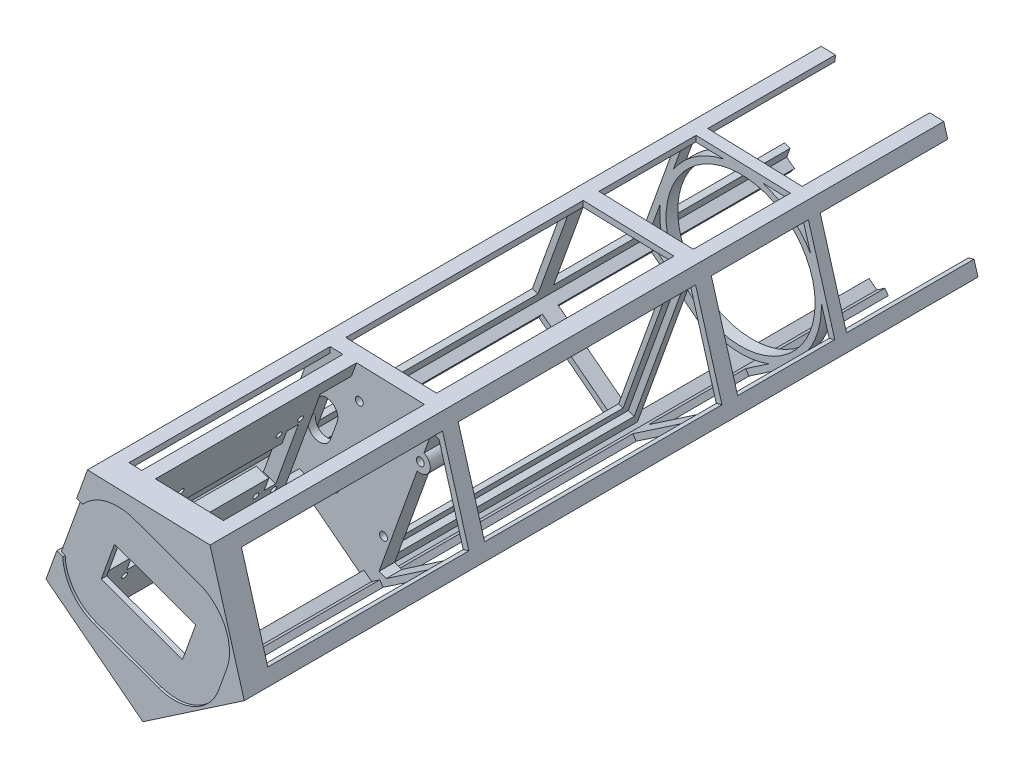
SolidWorks part; units mm, degrees
ref_plane "Front Plane" through (0, 0, 0) normal (0, 0, 1) x (1, 0, 0)
ref_plane "Top Plane" through (0, 0, 0) normal (0, 1, 0) x (1, 0, 0)
ref_plane "Right Plane" through (0, 0, 0) normal (1, 0, 0) x (0, 0, -1)
sketch "Sketch3" plane through (0, 0, 0) normal (0, 0, 1) x (1, 0, 0)
  line L0 (0, 0) -> (16.2851, 21.0012) construction
  line L1 (15.1489, 19.536) -> (-13.8986, 20.4445)
  line L2 (-13.8986, 20.4445) -> (-23.7387, -6.9006)
  line L3 (-23.7387, -6.9006) -> (-0.7728, -24.7093)
  line L4 (-0.7728, -24.7093) -> (23.2611, -8.3705)
  line L5 (0, 0) -> (29.9163, 0) construction
  line L6 (0, 0) -> (25.0057, -8.9983) construction
  line L10 (-0.8307, -26.5625) -> (25.0057, -8.9983)
  line L11 (25.0057, -8.9983) -> (16.2851, 21.0012)
  line L12 (16.2851, 21.0012) -> (-14.941, 21.9778)
  line L13 (-14.941, 21.9778) -> (-25.5191, -7.4182)
  line L14 (-25.5191, -7.4182) -> (-0.8307, -26.5625)
  line L15 (23.2611, -8.3705) -> (15.1489, 19.536)
  circle A0 centre (0, 0) radius 20 construction
  dimension "D2" = 40
extrude "Boss-Extrude2" add sketch "Sketch3" along normal blind 185
ref_plane "Plane1" through (0, 0, 92.5) normal (0, 0, 1) x (1, 0, 0)
sketch "Sketch4" plane through (0, 0, 0) normal (0, 0, -1) x (-1, 0, 0)
  line L0 (14.745, 18.0921) -> (16.1564, 18.6)
  line L1 (13.8986, 20.4445) -> (23.7387, -6.9006) construction
  line L2 (14.941, 21.9778) -> (25.5191, -7.4182) construction
  line L3 (24.3036, -4.0404) -> (22.8922, -4.5483)
  line L4 (22.8922, -4.5483) -> (14.745, 18.0921)
  line L5 (24.3036, -4.0404) -> (16.1564, 18.6)
  dimension "D1" = 2.5
  dimension "D2" = 2.5
extrude "Cut-Extrude1" cut sketch "Sketch4" against normal offset from surface (180 mm away) 5 up to face at (0, 0, 185)
ref_point "Point1"
ref_axis "Axis1" through (0, 0, 185) along (0, 0, 1)
pattern_circular "CirPattern1" count 5 over 360 about axis through (0, 0, 185) along (0, 0, 1) of "Cut-Extrude1"
ref_plane "Plane2" through (0, 0, 92.5) normal (0, 0, 1) x (1, 0, 0)
sketch "Sketch5" plane through (0, 0, 92.5) normal (0, 0, 1) x (1, 0, 0)
  line L0 (-2.0696, -25.6018) -> (14.7182, 21.0502) construction
  line L2 (-24.1133, -8.5083) -> (-1.8275, -25.7895) construction
  line L3 (23.2611, -8.3705) -> (0, 0) construction
  line L4 (-4.3961, -23.7977) -> (11.7756, 21.1422)
  line L8 (-2.0696, -25.6018) -> (-4.3961, -23.7977)
  line L10 (14.7182, 21.0502) -> (11.7756, 21.1422)
  line L11 (-2.0696, -25.6018) -> (14.7182, 21.0502)
  line L12 (-22.8004, 22.2236) -> (6.2471, 21.3151) construction
  dimension "D1" = 18
  dimension "D2" = 2.8
extrude "Boss-Extrude3" add sketch "Sketch5" along normal mid plane 64.5
sketch "Sketch6" plane through (0, 0, 124.75) normal (0, 0, 1) x (1, 0, 0)
  line L5 (-25.5191, -7.4182) -> (-0.8307, -26.5625)
  line L6 (-0.8307, -26.5625) -> (25.0057, -8.9983)
  line L7 (25.0057, -8.9983) -> (16.2851, 21.0012)
  line L8 (16.2851, 21.0012) -> (-14.941, 21.9778)
  line L9 (-14.941, 21.9778) -> (-25.5191, -7.4182)
  line L10 (-25.5191, -7.4182) -> (-0.8307, -26.5625)
  line L11 (-0.8307, -26.5625) -> (25.0057, -8.9983)
  line L12 (25.0057, -8.9983) -> (16.2851, 21.0012)
  line L13 (16.2851, 21.0012) -> (-14.941, 21.9778)
  line L14 (-14.941, 21.9778) -> (-25.5191, -7.4182)
  dimension "D1" = 0
extrude "Boss-Extrude4" add sketch "Sketch6" along normal blind 4
sketch "Sketch7" plane through (0, 0, 124.75) normal (0, 0, -1) x (-1, 0, 0)
  line L0 (-3.6897, -1.3278) -> (20.23, 7.2798) construction
  line L1 (-11.7756, 21.1422) -> (4.3961, -23.7977) construction
  line L2 (16.1564, 18.6) -> (24.3036, -4.0404) construction
  line L4 (19.0326, -2.4504) -> (13.1071, 14.0159)
  line L5 (0.2139, -9.2223) -> (-5.7115, 7.244)
  line L7 (19.0326, -2.4504) -> (-5.7115, 7.244) construction
  line L8 (0.2139, -9.2223) -> (13.1071, 14.0159) construction
  line L9 (9.6232, -5.8364) -> (3.6978, 10.63) construction
  line L11 (-11.7756, 21.1422) -> (4.3961, -23.7977) construction
  arc A0 (-5.7115, 7.244) -> (13.1071, 14.0159) centre (3.6978, 10.63) cw
  arc A1 (0.2139, -9.2223) -> (19.0326, -2.4504) centre (9.6232, -5.8364) ccw
  point P7 (6.6605, 2.3968)
  point P9 (13.0092, -15.2457)
  point P14 (0.3119, 20.0393)
  dimension "D1" = 37.5
  dimension "D2" = 20
  dimension "D3" = 1
extrude "Cut-Extrude2" cut sketch "Sketch7" against normal blind 2
sketch "Sketch8" plane through (6.3243, -2.2758, 0) normal (0.9409, -0.3386, 0) x (0, 0, -1)
  line L0 (-60.25, 0) -> (-124.75, 0) construction
  line L1 (-124.75, -23.2131) -> (-124.75, 23.2131) construction
  line L3 (-60.25, -23.2131) -> (-60.25, 23.2131) construction
  line L5 (-123, -20.5) -> (-123, 20.5)
  line L6 (-123, -20.5) -> (-62, -20.5)
  line L7 (-123, 20.5) -> (-62, 20.5)
  line L8 (-62, -20.5) -> (-62, 20.5)
  line L14 (-62, 20.5) -> (-123, -20.5) construction
  line L15 (-62, -20.5) -> (-123, 20.5) construction
  point P11 (-92.5, 0)
  point P14 (-92.5, 0)
  dimension "D1" = 61
  dimension "D2" = 41
extrude "Cut-Extrude3" cut sketch "Sketch8" against normal blind 1.6
sketch "Sketch9" plane through (4.8189, -1.7341, 0) normal (0.9409, -0.3386, 0) x (0, 0, -1)
  line L8 (-121, -18.5) -> (-64, -18.5)
  line L9 (-64, -18.5) -> (-64, 18.5)
  line L10 (-64, 18.5) -> (-121, 18.5)
  line L11 (-121, 18.5) -> (-121, -18.5)
  line L12 (-121, -18.5) -> (-64, -18.5)
  line L13 (-64, -18.5) -> (-64, 18.5)
  line L14 (-64, 18.5) -> (-121, 18.5)
  line L15 (-121, 18.5) -> (-121, -18.5)
  dimension "D1" = 2
extrude "Cut-Extrude4" cut sketch "Sketch9" against normal up to surface (1.2 mm away) up to face at (3.6897, -1.3278, 92.5)
sketch "Sketch10" plane through (0, 0, 60.25) normal (0, 0, -1) x (-1, 0, 0)
  line L25 (-23.2611, -8.3705) -> (0.7728, -24.7093)
  line L26 (0.7728, -24.7093) -> (23.7387, -6.9006)
  line L27 (23.7387, -6.9006) -> (13.8986, 20.4445)
  line L28 (13.8986, 20.4445) -> (-15.1489, 19.536)
  line L29 (-15.1489, 19.536) -> (-23.2611, -8.3705)
  line L30 (0.8307, -26.5625) -> (25.5191, -7.4182)
  line L31 (-25.0057, -8.9983) -> (0.8307, -26.5625)
  line L32 (-16.2851, 21.0012) -> (-25.0057, -8.9983)
  line L33 (14.941, 21.9778) -> (-16.2851, 21.0012)
  line L34 (25.5191, -7.4182) -> (14.941, 21.9778)
  line L40 (0.8307, -26.5625) -> (25.5191, -7.4182)
  line L41 (-25.0057, -8.9983) -> (0.8307, -26.5625)
  line L42 (-16.2851, 21.0012) -> (-25.0057, -8.9983)
  line L43 (14.941, 21.9778) -> (-16.2851, 21.0012)
  line L44 (25.5191, -7.4182) -> (14.941, 21.9778)
  dimension "D1" = 0
extrude "Boss-Extrude5" add sketch "Sketch10" against normal blind 4
sketch "Sketch11" plane through (0, 0, 60.25) normal (0, 0, -1) x (-1, 0, 0)
  line L0 (3.8621, -22.3137) -> (4.3961, -23.7977)
  line L1 (4.3961, -23.7977) -> (3.6676, -24.3627)
  line L2 (-11.2416, 19.6582) -> (-11.7756, 21.1422)
  line L3 (-11.7756, 21.1422) -> (-12.697, 21.1134)
  line L4 (21.7631, -8.4326) -> (3.8621, -22.3137)
  line L7 (3.8621, -22.3137) -> (-11.2416, 19.6582)
  line L9 (-14.1842, 19.5662) -> (1.5355, -24.1178)
  line L10 (-14.1842, 19.5662) -> (1.5355, -24.1178)
  line L11 (-12.697, 21.1134) -> (11.3529, 21.8656) construction
  line L13 (3.8621, -22.3137) -> (-11.2416, 19.6582) construction
  line L18 (22.6823, -9.618) -> (3.6676, -24.3627) construction
  line L19 (3.8621, -22.3137) -> (-11.2416, 19.6582)
  line L27 (-11.2416, 19.6582) -> (11.3998, 20.3663)
  line L31 (1.5355, -24.1178) -> (2.7484, -23.1773)
  line L33 (1.5355, -24.1178) -> (2.7484, -23.1773)
  line L35 (2.7484, -23.1773) -> (3.6676, -24.3627)
  line L37 (2.7484, -23.1773) -> (3.6676, -24.3627)
  line L39 (3.6676, -24.3627) -> (22.6823, -9.618)
  line L41 (22.6823, -9.618) -> (21.7631, -8.4326)
  line L43 (11.3998, 20.3663) -> (11.3529, 21.8656)
  line L45 (11.3529, 21.8656) -> (-12.697, 21.1134)
  line L47 (-12.697, 21.1134) -> (-12.6502, 19.6141)
  line L48 (-12.697, 21.1134) -> (-12.6502, 19.6141)
  line L49 (-12.6502, 19.6141) -> (-14.1842, 19.5662)
  line L50 (-12.6502, 19.6141) -> (-14.1842, 19.5662)
  dimension "D1" = 0
ref_plane "Plane3" through (0, 0, 32.5) normal (0, 0, 1) x (1, 0, 0)
sketch "Sketch14" plane through (0, 0, 32.5) normal (0, 0, 1) x (1, 0, 0)
  line L5 (-25.5191, -7.4182) -> (-0.8307, -26.5625)
  line L6 (-0.8307, -26.5625) -> (25.0057, -8.9983)
  line L7 (25.0057, -8.9983) -> (16.2851, 21.0012)
  line L8 (16.2851, 21.0012) -> (-14.941, 21.9778)
  line L9 (-14.941, 21.9778) -> (-25.5191, -7.4182)
  line L11 (-0.8307, -26.5625) -> (25.0057, -8.9983)
  line L12 (25.0057, -8.9983) -> (16.2851, 21.0012)
  line L16 (23.2611, -8.3705) -> (15.3259, -13.7651)
  line L18 (-0.7728, -24.7093) -> (-8.3554, -18.8294)
  line L20 (-23.7387, -6.9006) -> (-20.4898, 2.1279)
  line L22 (-13.8986, 20.4445) -> (-4.308, 20.1445)
  line L24 (15.1489, 19.536) -> (17.8273, 10.3221)
  line L25 (7.1625, -19.3147) -> (-0.7728, -24.7093)
  line L26 (20.5827, 0.8433) -> (23.2611, -8.3705)
  line L27 (5.5584, 19.8359) -> (15.1489, 19.536)
  line L28 (-17.1475, 11.416) -> (-13.8986, 20.4445)
  line L29 (-16.1561, -12.7805) -> (-23.7387, -6.9006)
  line L30 (16.2851, 21.0012) -> (-14.941, 21.9778)
  line L31 (-14.941, 21.9778) -> (-25.5191, -7.4182)
  line L32 (-25.5191, -7.4182) -> (-0.8307, -26.5625)
  circle A3 centre (0, 0) radius 19
  arc A8 (15.3259, -13.7651) -> (20.5827, 0.8433) centre (0, 0) ccw
  circle A9 centre (0, 0) radius 20.6 construction
  arc A10 (17.8273, 10.3221) -> (5.5584, 19.8359) centre (0, 0) ccw
  arc A11 (-4.308, 20.1445) -> (-17.1475, 11.416) centre (0, 0) ccw
  arc A12 (-20.4898, 2.1279) -> (-16.1561, -12.7805) centre (0, 0) ccw
  arc A13 (-8.3554, -18.8294) -> (7.1625, -19.3147) centre (0, 0) ccw
  dimension "D2" = 38
  dimension "D1" = 0
  dimension "D3" = 1.6
extrude "Boss-Extrude8" add sketch "Sketch14" along normal blind 3
ref_plane "Plane4" through (0, 0, 29.5) normal (0, 0, -1) x (-1, 0, 0)
sketch "Sketch15" plane through (0, 0, 29.5) normal (0, 0, -1) x (-1, 0, 0)
  line L0 (-23.2611, -8.3705) -> (0.7728, -24.7093)
  line L1 (0.7728, -24.7093) -> (23.7387, -6.9006)
  line L2 (23.7387, -6.9006) -> (13.8986, 20.4445)
  line L3 (13.8986, 20.4445) -> (-15.1489, 19.536)
  line L4 (-15.1489, 19.536) -> (-23.2611, -8.3705)
  line L5 (0.8307, -26.5625) -> (25.5191, -7.4182)
  line L6 (-25.0057, -8.9983) -> (0.8307, -26.5625)
  line L7 (-16.2851, 21.0012) -> (-25.0057, -8.9983)
  line L8 (14.941, 21.9778) -> (-16.2851, 21.0012)
  line L9 (25.5191, -7.4182) -> (14.941, 21.9778)
  line L10 (0.8307, -26.5625) -> (25.5191, -7.4182)
  line L11 (-25.0057, -8.9983) -> (0.8307, -26.5625)
  line L12 (-16.2851, 21.0012) -> (-25.0057, -8.9983)
  line L13 (14.941, 21.9778) -> (-16.2851, 21.0012)
  line L14 (25.5191, -7.4182) -> (14.941, 21.9778)
  dimension "D1" = 0
sketch "Sketch29" plane through (0, 0, 185) normal (0, 0, 1) x (1, 0, 0)
  line L5 (-25.5191, -7.4182) -> (-0.8307, -26.5625)
  line L6 (-0.8307, -26.5625) -> (25.0057, -8.9983)
  line L7 (25.0057, -8.9983) -> (16.2851, 21.0012)
  line L8 (16.2851, 21.0012) -> (-14.941, 21.9778)
  line L9 (-14.941, 21.9778) -> (-25.5191, -7.4182)
  line L10 (-25.5191, -7.4182) -> (-0.8307, -26.5625)
  line L11 (-0.8307, -26.5625) -> (25.0057, -8.9983)
  line L12 (25.0057, -8.9983) -> (16.2851, 21.0012)
  line L13 (16.2851, 21.0012) -> (-14.941, 21.9778)
  line L14 (-14.941, 21.9778) -> (-25.5191, -7.4182)
  dimension "D1" = 0
extrude "Boss-Extrude13" add sketch "Sketch29" along normal blind 2
sketch "Sketch30" plane through (0, 0, 187) normal (0, 0, 1) x (1, 0, 0)
  line L0 (25.0057, -8.9983) -> (-20.23, 7.2798) construction
  line L1 (-14.941, 21.9778) -> (-25.5191, -7.4182) construction
  line L2 (3.1542, -17.0767) -> (-13.3121, -11.1513)
  line L3 (18.5086, -9.8487) -> (20.5401, -4.2031)
  line L4 (-20.5401, 4.2031) -> (-18.5086, 9.8487)
  line L5 (13.3121, 11.1513) -> (-3.1542, 17.0767)
  line L6 (14.4454, -21.1398) -> (-14.4454, 21.1398) construction
  line L7 (-24.6033, -7.0881) -> (24.6033, 7.0881) construction
  line L8 (19.5243, -7.0259) -> (-19.5243, 7.0259) construction
  arc A0 (18.5086, -9.8487) -> (3.1542, -17.0767) centre (7.2174, -5.7855) cw
  arc A1 (-18.5086, 9.8487) -> (-3.1542, 17.0767) centre (-7.2174, 5.7855) cw
  arc A2 (-13.3121, -11.1513) -> (-20.5401, 4.2031) centre (-9.2489, 0.1399) cw
  arc A3 (20.5401, -4.2031) -> (13.3121, 11.1513) centre (9.2489, -0.1399) ccw
  point P5 (0, 0)
  dimension "D3" = 12
  dimension "D1" = 30
  dimension "D2" = 41.5
extrude "Cut-Extrude8" cut sketch "Sketch30" against normal blind 0.6
sketch "Sketch31" plane through (0, 0, 186.4) normal (0, 0, 1) x (1, 0, 0)
  line L0 (25.0057, -8.9983) -> (0, 0) construction
  line L1 (12.0432, 0.9801) -> (8.6573, -8.4292)
  line L2 (12.0432, 0.9801) -> (-8.6573, 8.4292)
  line L3 (8.6573, -8.4292) -> (-12.0432, -0.9801)
  line L4 (-8.6573, 8.4292) -> (-12.0432, -0.9801)
  line L5 (12.0432, 0.9801) -> (-12.0432, -0.9801) construction
  line L6 (8.6573, -8.4292) -> (-8.6573, 8.4292) construction
  line L7 (-10.3503, 3.7246) -> (10.3503, -3.7246) construction
  dimension "D1" = 22
  dimension "D2" = 10
extrude "Cut-Extrude9" cut sketch "Sketch31" against normal up to surface (1.4 mm away) up to face at (0, 0, 185)
sketch "Sketch32" plane through (0, 0, 187) normal (0, 0, 1) x (1, 0, 0)
  line L0 (0, 0) -> (-36.3954, 13.0969) construction
  line L1 (-22.7695, 0.2228) -> (-21.2398, -0.3276)
  line L3 (-14.941, 21.9778) -> (-25.5191, -7.4182) construction
  line L4 (-17.6906, 14.3368) -> (-16.1609, 13.7863)
  line L5 (-18.5086, 9.8487) -> (-20.5401, 4.2031) construction
  line L6 (-18.5086, 9.8487) -> (-20.5401, 4.2031)
  line L7 (-17.6906, 14.3368) -> (-22.7695, 0.2228)
  arc A0 (-20.5401, 4.2031) -> (-13.3121, -11.1513) centre (-9.2489, 0.1399) ccw construction
  arc A1 (-20.5401, 4.2031) -> (-13.3121, -11.1513) centre (-9.2489, 0.1399) ccw construction
  arc A3 (-3.1542, 17.0767) -> (-18.5086, 9.8487) centre (-7.2174, 5.7855) ccw construction
  arc A4 (-16.1609, 13.7863) -> (-18.5086, 9.8487) centre (-7.2174, 5.7855) ccw
  arc A5 (-20.5401, 4.2031) -> (-21.2398, -0.3276) centre (-9.2489, 0.1399) ccw
  dimension "D1" = 7.5
extrude "Cut-Extrude11" cut sketch "Sketch32" against normal up to surface (0.6 mm away) up to face at (0, 0, 186.4)
sketch "Sketch34" plane through (0, 0, 186.4) normal (0, 0, 1) x (1, 0, 0)
  line L0 (-22.7695, 0.2228) -> (-17.6906, 14.3368)
  line L1 (-22.7695, 0.2228) -> (-22.0638, -0.0311)
  line L2 (-17.6906, 14.3368) -> (-16.9849, 14.0828)
  line L3 (-22.0638, -0.0311) -> (-16.9849, 14.0828)
  line L4 (-13.3121, -11.1513) -> (3.1542, -17.0767)
  line L5 (18.5086, -9.8487) -> (20.5401, -4.2031)
  line L6 (13.3121, 11.1513) -> (-3.1542, 17.0767)
  line L7 (-18.5086, 9.8487) -> (-20.5401, 4.2031)
  line L8 (-13.3121, -11.1513) -> (3.1542, -17.0767) construction
  line L9 (18.5086, -9.8487) -> (20.5401, -4.2031) construction
  line L10 (13.3121, 11.1513) -> (-3.1542, 17.0767) construction
  line L11 (-18.5086, 9.8487) -> (-20.5401, 4.2031) construction
  arc A4 (3.1542, -17.0767) -> (18.5086, -9.8487) centre (7.2174, -5.7855) ccw
  arc A5 (20.5401, -4.2031) -> (13.3121, 11.1513) centre (9.2489, -0.1399) ccw
  arc A6 (-3.1542, 17.0767) -> (-18.5086, 9.8487) centre (-7.2174, 5.7855) ccw
  arc A7 (-20.5401, 4.2031) -> (-13.3121, -11.1513) centre (-9.2489, 0.1399) ccw
  arc A8 (3.1542, -17.0767) -> (18.5086, -9.8487) centre (7.2174, -5.7855) ccw construction
  arc A9 (20.5401, -4.2031) -> (13.3121, 11.1513) centre (9.2489, -0.1399) ccw construction
  arc A10 (-3.1542, 17.0767) -> (-18.5086, 9.8487) centre (-7.2174, 5.7855) ccw construction
  arc A11 (-20.5401, 4.2031) -> (-13.3121, -11.1513) centre (-9.2489, 0.1399) ccw construction
  dimension "D1" = 0
sketch "Sketch38" plane through (0, 0, 124.75) normal (0, 0, -1) x (-1, 0, 0)
  line L5 (13.8986, 20.4445) -> (-15.1489, 19.536)
  line L6 (-15.1489, 19.536) -> (-23.2611, -8.3705)
  line L7 (-23.2611, -8.3705) -> (0.7728, -24.7093)
  line L8 (0.7728, -24.7093) -> (23.7387, -6.9006)
  line L9 (23.7387, -6.9006) -> (13.8986, 20.4445)
  line L11 (-16.3988, 15.2363) -> (-23.2611, -8.3705)
  line L12 (-23.2611, -8.3705) -> (-2.9303, -22.1919)
  line L16 (-1.0956, -21.5316) -> (-2.9303, -22.1919)
  line L17 (0.03, -24.6596) -> (-15.6897, 19.0244)
  line L18 (-1.0956, -21.5316) -> (-14.5641, 15.8965)
  line L19 (-14.5641, 15.8965) -> (-16.3988, 15.2363)
  dimension "D3" = 1.6
  dimension "D4" = 1.6
  dimension "D1" = 0
  dimension "D2" = 1.6
extrude "Cut-Extrude14" cut sketch "Sketch38" against normal up to surface (4 mm away) up to face at (0, 0, 128.75)
sketch "Sketch40" plane through (-18.8186, 6.7719, 0) normal (0.9409, -0.3386, 0) x (0, 0, -1)
  line L0 (-185, 14.5309) -> (-185, -14.5309) construction
  line L1 (-185, 7.5) -> (-183.5, 7.5)
  line L2 (-185, 7.5) -> (-185, -7.5)
  line L3 (-185, -7.5) -> (-183.5, -7.5)
  line L4 (-183.5, 7.5) -> (-183.5, -7.5)
  line L5 (-183.5, 0) -> (-185, 0) construction
  point P9 (-185, 0)
  dimension "D1" = 15
  dimension "D2" = 1.5
extrude "Cut-Extrude15" cut sketch "Sketch40" against normal up to surface (1.5 mm away) up to face at (-20.23, 7.2798, 98.8167)
sketch "Sketch41" plane through (-20.23, 7.2798, 0) normal (-0.9409, 0.3386, 0) x (0, 0, 1)
  line L0 (185, -7.5) -> (186.4, -7.5)
  line L1 (185, 7.5) -> (186.4, 7.5)
  line L2 (185, -7.5) -> (185, 7.5)
  line L3 (186.4, 7.5) -> (186.4, -7.5)
extrude "Cut-Extrude16" cut sketch "Sketch41" against normal blind 0.6
ref_plane "Plane5" through (14.5641, 15.8965, 124.75) normal (0.3386, 0.9409, 0) x (0.9409, -0.3386, 0)
sketch "Sketch42" plane through (0, 0, 128.75) normal (0, 0, 1) x (1, 0, 0)
  line L0 (-20.23, 7.2798) -> (0, 0) construction
  line L1 (-16.1564, 18.6) -> (-24.3036, -4.0404) construction
  line L2 (5.4365, -16.774) -> (-14.8782, -9.4637) construction
  line L3 (5.4365, -16.774) -> (14.8782, 9.4637) construction
  line L4 (-14.8782, -9.4637) -> (-5.4365, 16.774) construction
  line L5 (14.8782, 9.4637) -> (-5.4365, 16.774) construction
  line L6 (5.4365, -16.774) -> (-5.4365, 16.774) construction
  line L7 (-14.8782, -9.4637) -> (14.8782, 9.4637) construction
  line L8 (-3.9066, 13.524) -> (11.6282, 7.9338) construction
  line L9 (4.7208, 13.1189) -> (-4.7208, -13.1189) construction
  line L10 (2.2472, -13.2032) -> (-10.1449, -8.7439) construction
  line L11 (-1.5355, -24.1178) -> (14.1842, 19.5662) construction
  line L12 (-1.5355, -24.1178) -> (14.1842, 19.5662)
  line L13 (12.891, 3.9416) -> (6.1392, -14.8212) construction
  line L14 (12.891, 3.9416) -> (10.6328, 4.7542) construction
  line L15 (6.1392, -14.8212) -> (3.881, -14.0086) construction
  line L16 (10.6328, 4.7542) -> (3.881, -14.0086) construction
  circle A0 centre (11.6282, 7.9338) radius 1
  circle A1 centre (-3.9066, 13.524) radius 1
  circle A2 centre (2.2472, -13.2032) radius 1
  circle A3 centre (-10.1449, -8.7439) radius 1
  point P1 (3.8608, 10.7289)
  point P2 (0, 0)
  point P19 (-3.9488, -10.9735)
  dimension "D4" = 2
  dimension "D7" = 2
  dimension "D1" = 21.59
  dimension "D2" = 27.8848
  dimension "D3" = 16.51
  dimension "D5" = 2.54
  dimension "D6" = 13.17
  dimension "D8" = 2.28
  dimension "D9" = 2.4
sketch "Sketch43" plane through (0, 0, 128.75) normal (0, 0, 1) x (1, 0, 0)
  line L1 (10.8306, 5.5214) -> (12.5507, 10.3013)
  line L2 (12.891, 3.9416) -> (10.6328, 4.7542) construction
  line L3 (12.891, 3.9416) -> (10.6328, 4.7542)
  line L4 (1.0956, -21.5316) -> (14.5641, 15.8965) construction
  arc A0 (12.5507, 10.3013) -> (10.8306, 5.5214) centre (11.6282, 7.9338) cw
  point P4 (12.5507, 10.3013)
  line M27 (1.0956, -21.5316) -> (14.5641, 15.8965)
  dimension "D1" = 2.5409
extrude "Boss-Extrude15" add sketch "Sketch43" against normal up to surface (4 mm away) contours A0 M27 region at (12.6767, 7.5565, 128.75) up to face at (11.7736, -4.2367, 124.75)
sketch "Sketch44" plane through (0, 0, 128.75) normal (0, 0, 1) x (1, 0, 0)
  circle A0 centre (-10.1449, -8.7439) radius 1 construction
  circle A1 centre (-3.9066, 13.524) radius 1 construction
  circle A2 centre (-10.1449, -8.7439) radius 1
  circle A3 centre (-3.9066, 13.524) radius 1
extrude "Cut-Extrude18" cut sketch "Sketch42" against normal blind 3.5 contours A0 | A2
extrude "Cut-Extrude19" cut sketch "Sketch44" against normal blind 1.5
sketch "Sketch45" plane through (0, 0, 128.75) normal (0, 0, 1) x (1, 0, 0)
  line L0 (-2.5743, -18.735) -> (9.9537, 16.0795) construction
  line L1 (-2.5743, -18.735) -> (9.9537, 16.0795) construction
  line L2 (13.2655, 17.0133) -> (-0.6169, -21.5649) construction
  line L3 (13.2655, 17.0133) -> (-0.6169, -21.5649) construction
  line L4 (-4.3961, -23.7977) -> (11.7756, 21.1422)
  line L5 (11.7756, 21.1422) -> (14.7182, 21.0502)
  line L6 (14.7182, 21.0502) -> (-2.0696, -25.6018)
  line L7 (-2.0696, -25.6018) -> (-4.3961, -23.7977)
  line L8 (-22.6823, -9.618) -> (-3.6676, -24.3627) construction
  line L11 (12.697, 21.1134) -> (-11.3529, 21.8656) construction
sketch "Sketch46" plane through (0, 0, 128.75) normal (0, 0, 1) x (1, 0, 0)
  line L0 (-8.1098, 21.7641) -> (-20.1403, -11.5891)
  line L1 (-8.1098, 21.7641) -> (-4.6098, 21.6547)
  line L2 (-20.1403, -11.5891) -> (-17.3745, -13.7339)
  line L3 (-4.6098, 21.6547) -> (-17.3745, -13.7339)
  line L4 (-16.1564, 18.6) -> (-24.3036, -4.0404) construction
  line L5 (-1.5355, -24.1178) -> (14.1842, 19.5662) construction
  line L6 (-1.5355, -24.1178) -> (14.1842, 19.5662)
  line L8 (12.697, 21.1134) -> (-11.3529, 21.8656) construction
  line L9 (-22.6823, -9.618) -> (-3.6676, -24.3627) construction
  line M13 (12.697, 21.1134) -> (-11.3529, 21.8656)
  line M23 (-22.6823, -9.618) -> (-3.6676, -24.3627)
  dimension "D1" = 3.5
  dimension "D2" = 3.5
  dimension "D3" = 6.5
extrude "Boss-Extrude17" add sketch "Sketch46" along normal up to surface (56.25 mm away) contours L3 L0 M13 M23 region at (-12.5431, 4.5184, 128.75) up to face at (-8.552, 3.0775, 185)
sketch "Sketch48" plane through (-14.1227, 5.0941, 0) normal (-0.9407, 0.3393, 0) x (0, 0, 1)
  line L0 (128.75, 18.8059) -> (128.75, -18.8143) construction
  line L1 (128.75, -15) -> (136.75, -15)
  line L2 (128.75, -15) -> (128.75, 15)
  line L3 (128.75, 15) -> (136.75, 15)
  line L4 (136.75, -15) -> (136.75, 15)
  line L5 (128.75, -15) -> (136.75, 15) construction
  line L6 (128.75, 15) -> (136.75, -15) construction
  line L7 (-3.5596, 0) -> (269.0596, 0) construction
  point P0 (132.75, 0)
  dimension "D1" = 8
  dimension "D2" = 30
extrude "Cut-Extrude20" cut sketch "Sketch48" against normal up to surface (3.3295 mm away) up to face at (-10.9922, 3.9602, 168.4375)
sketch "Sketch49" plane through (0, 0, 126.75) normal (0, 0, -1) x (-1, 0, 0)
  line L0 (-2.7488, -0.9892) -> (16.0698, 5.7828) construction
  line L1 (-5.7115, 7.244) -> (0.2139, -9.2223) construction
  line L2 (19.0326, -2.4504) -> (13.1071, 14.0159) construction
  line L3 (12.4006, 7.1193) -> (14.0935, 2.4146) construction
  line L4 (15.2234, 8.1351) -> (16.9163, 3.4304)
  line L5 (9.5778, 6.1035) -> (11.2707, 1.3988)
  arc A0 (15.2234, 8.1351) -> (9.5778, 6.1035) centre (12.4006, 7.1193) ccw
  arc A1 (11.2707, 1.3988) -> (16.9163, 3.4304) centre (14.0935, 2.4146) ccw
  point P8 (13.247, 4.767)
  dimension "D1" = 6
  dimension "D2" = 5
extrude "Cut-Extrude21" cut sketch "Sketch49" against normal up to surface (10 mm away) up to face at (-12.5567, 4.5292, 136.75)
sketch "Sketch50" plane through (-14.1227, 5.0941, 0) normal (-0.9407, 0.3393, 0) x (0, 0, 1)
  line L0 (136.75, 0) -> (181.403, 0) construction
  line L1 (138.0765, -12.1) -> (180.0765, -12.1) construction
  line L2 (138.0765, -12.1) -> (138.0765, 12.1) construction
  line L3 (138.0765, 12.1) -> (180.0765, 12.1) construction
  line L4 (180.0765, -12.1) -> (180.0765, 12.1) construction
  line L5 (138.0765, -12.1) -> (180.0765, 12.1) construction
  line L6 (138.0765, 12.1) -> (180.0765, -12.1) construction
  line L7 (136.75, -15) -> (136.75, 15) construction
  line L8 (159.0765, 12.1) -> (159.0765, -12.1) construction
  circle A0 centre (178.0765, -10.1) radius 0.75
  circle A1 centre (178.0765, 10.1) radius 0.75
  circle A2 centre (140.0765, -10.1) radius 0.75
  circle A3 centre (140.0765, 10.1) radius 0.75
  point P0 (159.0765, 0)
  point P5 (178.0765, -10.85)
  point P6 (178.8265, -10.1)
  dimension "D3" = 1.5
  dimension "D4" = 1.25
  dimension "D1" = 24.2
  dimension "D2" = 42
  dimension "D5" = 1.25
extrude "Cut-Extrude22" cut sketch "Sketch50" against normal up to surface (3.3295 mm away) up to face at (-10.9917, 3.9616, 156.5417)
sketch "Sketch51" plane through (-14.1227, 5.0941, 0) normal (-0.9407, 0.3393, 0) x (0, 0, 1)
  line L0 (180, 0) -> (103.153, 0) construction
  line L1 (143.0765, -8.5) -> (140.0765, -8.5)
  line L2 (143.0765, -8.5) -> (143.0765, -4.9557)
  line L3 (143.0765, 8.5) -> (140.0765, 8.5)
  line L4 (140.0765, -8.5) -> (140.0765, 8.5)
  line L5 (143.0765, -8.5) -> (140.0765, 8.5) construction
  line L6 (143.0765, 8.5) -> (140.0765, -8.5) construction
  line L7 (180, -12.047) -> (180, 12.0147) construction
  line L8 (140.0765, 10.1) -> (140.0765, -10.1) construction
  line L9 (178.0765, 10.1) -> (178.0765, 5.0443) construction
  line L10 (140.0765, 10.1) -> (178.0765, -10.1) construction
  line L11 (140.0765, -10.1) -> (178.0765, 10.1) construction
  line L12 (159.0765, 10.1) -> (159.0765, -10.1) construction
  line L13 (175.0765, 8.5) -> (178.0765, 8.5)
  line L14 (178.0765, -8.5) -> (178.0765, -4.9557)
  line L15 (175.0765, -8.5) -> (178.0765, -8.5)
  line L16 (175.0765, -8.5) -> (175.0765, -4.9557)
  line L17 (143.0765, 5.0443) -> (175.0765, 5.0443)
  line L20 (143.0765, -4.9557) -> (175.0765, -4.9557)
  line L21 (143.0765, 5.0443) -> (175.0765, -4.9557) construction
  line L22 (175.0765, 5.0443) -> (143.0765, -4.9557) construction
  line L23 (143.0765, 5.0443) -> (143.0765, 8.5)
  line L24 (175.0765, 5.0443) -> (175.0765, 8.5)
  line L25 (178.0765, 5.0443) -> (185, 5.0443)
  line L26 (185, 5.0443) -> (185, -4.9557)
  line L27 (185, -4.9557) -> (178.0765, -4.9557)
  line L28 (178.0765, -4.9557) -> (178.0765, -10.1) construction
  line L29 (178.0765, 5.0443) -> (178.0765, 8.5)
  line L30 (185, 16.1438) -> (185, -16.1585) construction
  point P0 (141.5765, 0)
  point P21 (159.0765, 0)
  point P26 (159.0765, 0.0443)
  dimension "D1" = 17
  dimension "D2" = 10
  dimension "D3" = 3
  dimension "D4" = 3.5443
extrude "Cut-Extrude23" cut sketch "Sketch51" against normal up to surface (3.3295 mm away) up to face at (-7.3093, 14.1707, 178.0765)
sketch "Sketch52" plane through (-10.9907, 3.9644, 0) normal (0.9407, -0.3393, 0) x (0, 0, -1)
  line L0 (-170.0765, 8.75) -> (-170.0765, -8.75) construction
  line L1 (-140.0765, 0) -> (-178.0765, 0) construction
  line L2 (-140.0765, 8.5) -> (-140.0765, -8.5) construction
  line L3 (-178.0765, -8.5) -> (-178.0765, -4.9557) construction
  line L4 (-145.0765, 8.75) -> (-145.0765, -8.75) construction
  circle A0 centre (-170.0765, 8.75) radius 0.75
  circle A1 centre (-170.0765, -8.75) radius 0.75
  circle A2 centre (-145.0765, 8.75) radius 0.75
  circle A3 centre (-145.0765, -8.75) radius 0.75
  point P10 (-170.0765, 0)
  point P16 (-145.0765, 0)
  dimension "D1" = 1.5
  dimension "D2" = 17.5
  dimension "D3" = 8
  dimension "D4" = 25
extrude "Cut-Extrude24" cut sketch "Sketch52" against normal up to surface (3.3295 mm away) up to face at (-14.1191, 5.104, 161.199)
sketch "Sketch54" plane through (4.8189, -1.7341, 0) normal (0.9409, -0.3386, 0) x (0, 0, -1)
  line L0 (-62, 20.5) -> (-123, 20.5) construction
  line L1 (-123, 20.5) -> (-123, -20.5) construction
  line L2 (-64, 0) -> (-121, 0) construction
  line L3 (-64, -18.5) -> (-64, 18.5) construction
  line L4 (-121, 18.5) -> (-121, -18.5) construction
  line L5 (-92.5, 18.5) -> (-92.5, -18.5) construction
  line L6 (-64, 18.5) -> (-121, 18.5) construction
  line L7 (-121, -18.5) -> (-64, -18.5) construction
  circle A0 centre (-122, 19.5) radius 0.5
  circle A1 centre (-122, -19.5) radius 0.5
  circle A2 centre (-63, -19.5) radius 0.5
  circle A3 centre (-63, 19.5) radius 0.5
  dimension "D1" = 1
  dimension "D2" = 1
  dimension "D3" = 1
ref_plane "Plane8" through (15.2997, 42.5167, 0) normal (-0.3386, -0.9409, 0) x (-0.9409, 0.3386, 0)
